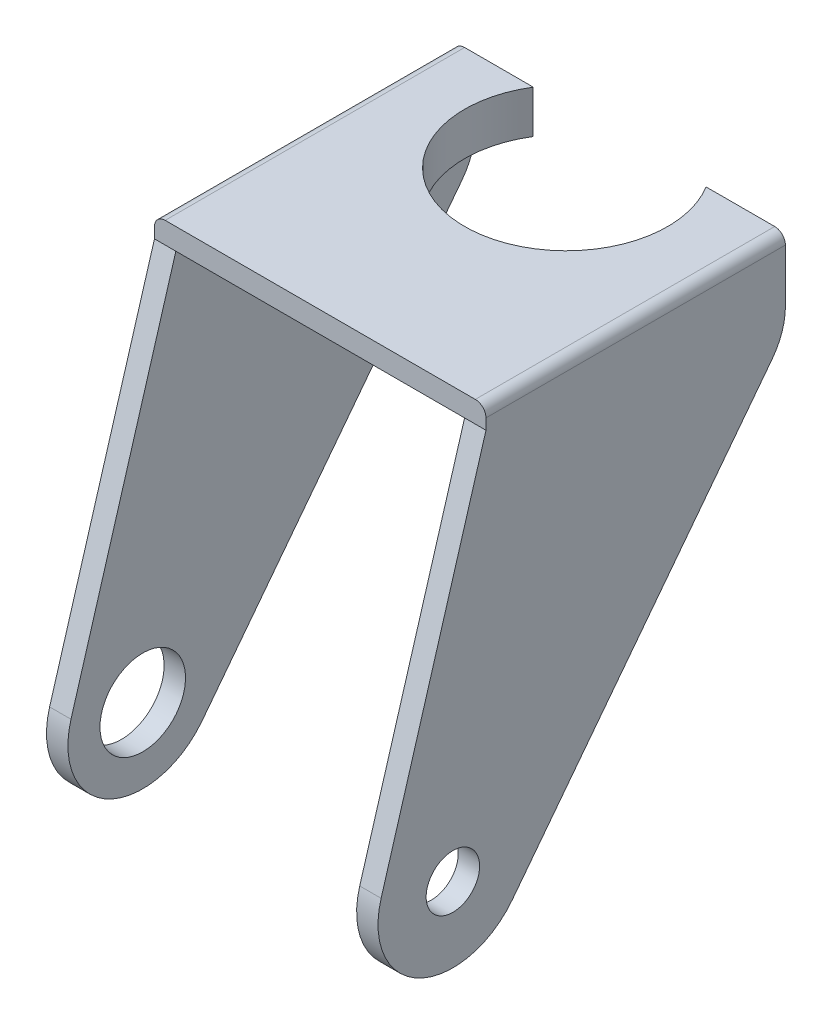
SolidWorks part; units mm, degrees
ref_plane "Front Plane" through (0, 0, 0) normal (0, 0, 1) x (1, 0, 0)
ref_plane "Top Plane" through (0, 0, 0) normal (0, 1, 0) x (1, 0, 0)
ref_plane "Right Plane" through (0, 0, 0) normal (1, 0, 0) x (0, 0, -1)
sketch "Sketch1" plane through (0, 0, 0) normal (1, 0, 0) x (0, 0, -1)
  line L0 (-6.71, 1.994) -> (3.0966, 34.994)
  line L1 (3.0966, 34.994) -> (3.0966, 36.994)
  line L2 (3.0966, 36.994) -> (31.0966, 36.994)
  line L3 (31.0966, 36.994) -> (31.0966, 31.0323)
  line L4 (29.8549, 27.3775) -> (5.5514, -4.264)
  arc A0 (-6.71, 1.994) -> (5.5514, -4.264) centre (0, 0) ccw
  arc A1 (31.0966, 31.0323) -> (29.8549, 27.3775) centre (25.0966, 31.0323) cw
  point P11 (31.0966, 28.994)
  dimension "D1" = 14
  dimension "D6" = 6
  dimension "D2" = 35
  dimension "D3" = 2
  dimension "D4" = 28
  dimension "D5" = 8
extrude "Boss-Extrude1" add sketch "Sketch1" against normal blind 2
ref_plane "Plane1" through (-15.5, 0, 0) normal (1, 0, 0) x (0, 0, -1)
mirror "Mirror1" about plane through (-15.5, 0, 0) normal (1, 0, 0) of bodies 101
sketch "Sketch2" plane through (0, 36.994, 0) normal (0, 1, 0) x (1, 0, 0)
  line L1 (-31, 31.0966) -> (0, 31.0966)
  line L2 (-31, 31.0966) -> (-31, 3.0966)
  line L3 (-31, 3.0966) -> (0, 3.0966)
  line L4 (0, 31.0966) -> (0, 3.0966)
extrude "Boss-Extrude2" add sketch "Sketch2" against normal blind 2
sketch "Sketch3" plane through (0, 36.994, 0) normal (0, 1, 0) x (1, 0, 0)
  line L0 (0, 17.0966) -> (-31, 17.0966) construction
  line L1 (0, 31.0966) -> (0, 3.0966) construction
  line L2 (-31, 31.0966) -> (-31, 3.0966) construction
  line L3 (-31, 17.0966) -> (-15.5, 3.0966) construction
  line L4 (-31, 3.0966) -> (0, 3.0966) construction
  line L5 (-15.5, 3.0966) -> (-15.5, 31.0966) construction
  line L6 (-31, 31.0966) -> (0, 31.0966) construction
  line L10 (-7.4196, 31.0923) -> (-5.1438, 31.0966)
  line L11 (-23.5804, 31.0923) -> (-25.8562, 31.0966)
  arc A0 (-23.5804, 31.0923) -> (-7.4196, 31.0923) centre (-15.5, 26.0966) ccw
  arc A1 (-25.8562, 31.0966) -> (-5.1438, 31.0966) centre (-15.5, 26.0966) ccw
  arc A2 (-25.2816, 32.144) -> (-5.7184, 32.144) centre (-15.5, 26.0966) ccw construction
  dimension "D3" = 19
  dimension "D5" = 2
extrude "Boss-Extrude3" add sketch "Sketch3" against normal blind 4
sketch "Sketch4" plane through (0, 34.994, 0) normal (0, -1, 0) x (1, 0, 0)
  line L3 (-5.1438, -31.0966) -> (-7.4196, -31.0923)
  line L4 (-23.5804, -31.0923) -> (-25.8562, -31.0966)
  line L5 (-25.8562, -31.0966) -> (-5.1438, -31.0966)
  line L6 (-5.1438, -31.0966) -> (-7.4196, -31.0923)
  line L7 (-23.5804, -31.0923) -> (-25.8562, -31.0966)
  line L8 (-25.8562, -31.0966) -> (-5.1438, -31.0966)
  arc A1 (-7.4196, -31.0923) -> (-23.5804, -31.0923) centre (-15.5, -26.0966) ccw
  arc A2 (-7.4196, -31.0923) -> (-23.5804, -31.0923) centre (-15.5, -26.0966) ccw
  dimension "D1" = 0
extrude "Cut-Extrude1" cut sketch "Sketch4" against normal blind 4
fillet "Fillet1" radius 1 2 edges at (-31, 36.994, -17.0966) (0, 36.994, -17.0966)
sketch "Sketch5" plane through (0, 0, 0) normal (1, 0, 0) x (0, 0, -1)
  circle A0 centre (0, 0) radius 4
  dimension "D1" = 8
extrude "Cut-Extrude2" cut sketch "Sketch5" against normal blind 10 from surface starting at face at (-29, 20.1542, -15.2809)
sketch "Sketch6" plane through (0, 0, 0) normal (1, 0, 0) x (0, 0, -1)
  circle A2 centre (0, 0) radius 2.5
  dimension "D1" = 5
extrude "Cut-Extrude3" cut sketch "Sketch6" against normal blind 10
scale "Scale1" scale about origin uniform scaling yes scale factor 0.5
